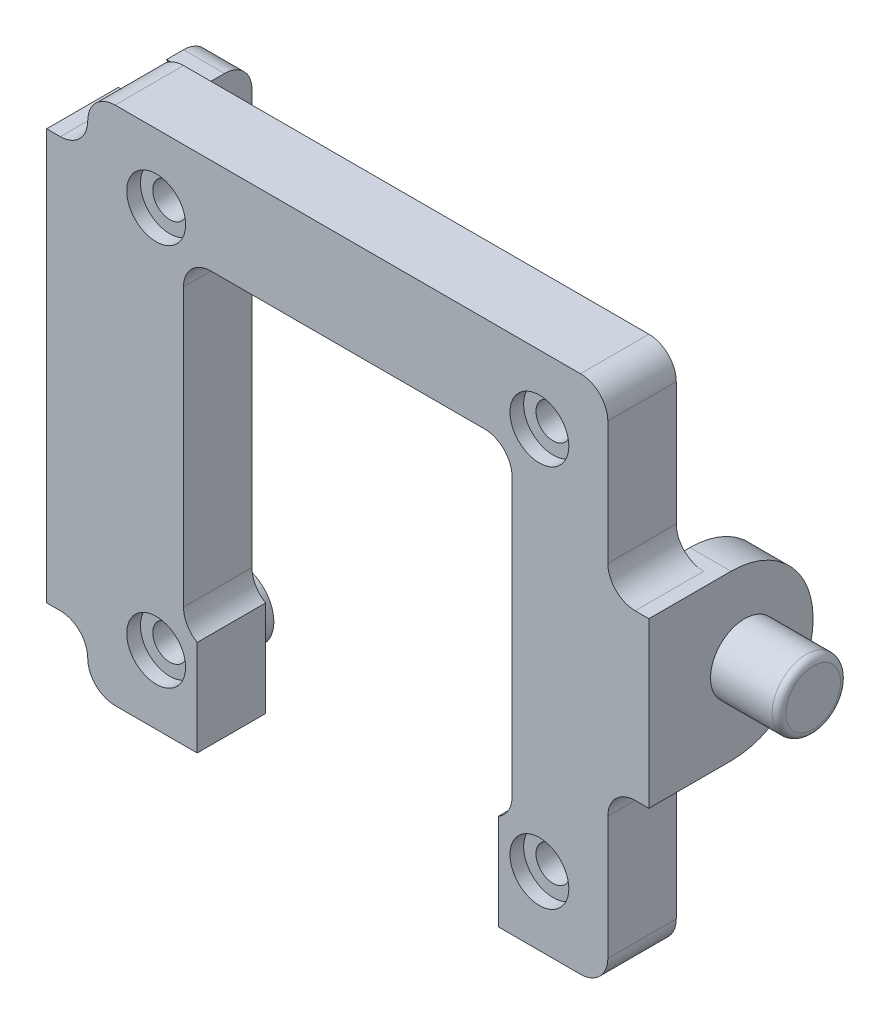
SolidWorks part; units mm, degrees
ref_plane "前视基准面" through (0, 0, 0) normal (0, 0, 1) x (1, 0, 0)
ref_plane "上视基准面" through (0, 0, 0) normal (0, 1, 0) x (1, 0, 0)
ref_plane "右视基准面" through (0, 0, 0) normal (1, 0, 0) x (0, 0, -1)
sketch "草图1" plane through (0, 0, 0) normal (0, 0, 1) x (1, 0, 0)
  line L0 (-14, 14) -> (14, 14) construction
  line L1 (19, -19) -> (12, -19)
  line L2 (19, -19) -> (19, 19)
  line L3 (19, 19) -> (-19, 19)
  line L4 (-19, -19) -> (-19, 19)
  line L5 (19, -19) -> (-19, 19) construction
  line L6 (19, 19) -> (-19, -19) construction
  line L7 (14, 14) -> (14, -14) construction
  line L8 (14, -14) -> (-14, -14) construction
  line L9 (-14, -14) -> (-14, 14) construction
  line L12 (12, -12) -> (12, 12)
  line L13 (12, 12) -> (-12, 12)
  line L14 (-12, -12) -> (-12, 12)
  line L15 (12, -12) -> (-12, 12) construction
  line L16 (12, 12) -> (-12, -12) construction
  line L18 (-12, -19) -> (-19, -19)
  line L19 (-12, -12) -> (-11, -12)
  line L20 (-11, -12) -> (-11, -19)
  line L21 (-11, -19) -> (-12, -19)
  line L22 (12, -12) -> (11, -12)
  line L23 (11, -12) -> (11, -19)
  line L24 (11, -19) -> (12, -19)
  circle A0 centre (-14, 14) radius 1 construction
  circle A1 centre (-14, -14) radius 1 construction
  circle A2 centre (14, -14) radius 1 construction
  circle A3 centre (14, 14) radius 1 construction
  point P0 (0, 0)
  point P14 (0, 0)
  dimension "D4" = 2
  dimension "D1" = 38
  dimension "D2" = 38
  dimension "D3" = 28
  dimension "D5" = 24
  dimension "D6" = 24
  dimension "D7" = 1
extrude "凸台-拉伸1" add sketch "草图1" against normal blind 5
sketch "草图6" plane through (0, 0, 0) normal (0, 0, 1) x (1, 0, 0)
  line L0 (-14, 14) -> (14, 14) construction
  line L5 (14, 14) -> (14, -14) construction
  line L6 (14, -14) -> (-14, -14) construction
  line L7 (-14, -14) -> (-14, 14) construction
  line L8 (-14, 14) -> (14, -14) construction
  line L9 (14, 14) -> (-14, -14) construction
  circle A0 centre (-14, 14) radius 2.5
  circle A1 centre (-14, -14) radius 2.5
  circle A2 centre (14, -14) radius 2.5
  circle A3 centre (14, 14) radius 2.5
  dimension "D4" = 5
  dimension "D1" = 28
  dimension "D2" = 28
extrude "凸台-拉伸5" add sketch "草图6" against normal blind 1.1 from surface starting at face at (0, -5.1667, -5)
hole_wizard "孔1" positions "草图2" profile "草图3" legacy end condition through all
sketch "草图2" plane through (0, 0, 0) normal (0, 0, 1) x (1, 0, 0)
  line L1 (14, -14) -> (-14, -14)
  line L2 (14, -14) -> (14, 14)
  line L3 (14, 14) -> (-14, 14)
  line L4 (-14, -14) -> (-14, 14)
  line L5 (14, -14) -> (-14, 14) construction
  line L6 (14, 14) -> (-14, -14) construction
  point P1 (-14, 14)
  point P148 (14, -14)
  point P149 (14, 14)
  point P150 (-14, -14)
  point P180 (0, 0)
  point P183 (0, 0)
  point P185 (0.0083, -0.0481)
  point P189 (0, 0)
  dimension "D1" = 28
  dimension "D2" = 28
sketch "草图3" plane through (-14, 14, 0) normal (1, 0, 0) x (0, -1, 0)
  line L0 (0, 0) -> (0, 6.1)
  line L1 (0, 6.1) -> (1.25, 6.1)
  line L2 (1.25, 6.1) -> (1.25, 1)
  line L3 (1.25, 1) -> (2.15, 1)
  line L4 (2.15, 1) -> (2.15, 0)
  line L5 (2.15, 0) -> (0, 0)
  line L6 (0, 110) -> (0, -10) construction
  dimension "直径" = 2.5
  dimension "深度" = 6.1
  dimension "柱坑直径" = 4.3
  dimension "柱坑深度" = 1
fillet "圆角1" radius 2 8 edges at (19, -19, -2.5) (19, 19, -2.5) (-19, 19, -2.5) (12, 12, -2.5) (-19, -19, -2.5) (12, -12, -2.5) (-12, -12, -2.5) (-12, 12, -2.5)
sketch "草图5" plane through (-19, 0, 0) normal (-1, 0, 0) x (0, 0, 1)
  line L0 (0, 17) -> (0, -17) construction
  line L1 (-12, -15) -> (0, -15)
  line L2 (-12, -15) -> (-12, 15)
  line L3 (-12, 15) -> (0, 15)
  line L4 (0, -15) -> (0, 15)
  line L5 (-12, -15) -> (0, 15) construction
  line L6 (-12, 15) -> (0, -15) construction
  line L7 (0, 0) -> (-6, 0) construction
  point P0 (-6, 0)
  dimension "D1" = 30
  dimension "D2" = 12
extrude "凸台-拉伸3" add sketch "草图5" along normal blind 3
sketch "草图9" plane through (-22, 0, -24) normal (1, 0, 0) x (0, 0, -1)
  line L0 (-17, 0) -> (-17, -14.05) construction
  line L1 (-18.997, -14.1591) -> (-19.65, -2.2091)
  line L2 (-14.35, -2.2091) -> (-15.003, -14.1591)
  line L3 (-12, 0) -> (-17, 0) construction
  line L4 (-12, 15) -> (-12, -15) construction
  line L5 (-24, -15) -> (-24, 15) construction
  arc A0 (-14.35, -2.2091) -> (-19.65, -2.2091) centre (-17, 0) ccw
  arc A1 (-18.997, -14.1591) -> (-15.003, -14.1591) centre (-17, -14.05) ccw
  dimension "D1" = 6.9
  dimension "D2" = 4
  dimension "D3" = 19.5
  dimension "D4" = 5.3
  dimension "D5" = 7
extrude "切除-拉伸1" cut sketch "草图9" along normal blind 1.4
mirror "镜向2" about plane through (0, 0, 0) normal (0, 1, 0) of "切除-拉伸1"
sketch "草图10" plane through (19, 0, 0) normal (1, 0, 0) x (0, 0, -1)
  line L0 (0, -17) -> (0, 17) construction
  line L1 (0, 6) -> (12, 6)
  line L2 (0, 6) -> (0, -6)
  line L3 (0, -6) -> (12, -6)
  line L4 (12, 6) -> (12, -6)
  line L5 (12, 15) -> (12, -15) construction
  line L6 (0, 0) -> (12, 0) construction
  dimension "D1" = 12
extrude "凸台-拉伸6" add sketch "草图10" along normal blind 3
sketch "草图11" plane through (22, 0, 0) normal (1, 0, 0) x (0, 0, -1)
  line L0 (0, 0) -> (7, 0) construction
  line L4 (0, 6) -> (0, -6)
  line L5 (0, -6) -> (12, -6)
  line L6 (12, -6) -> (12, 6)
  line L7 (12, 6) -> (0, 6)
  line L8 (0, 6) -> (0, -6) construction
  circle A0 centre (7, 0) radius 2.5
  dimension "D3" = 5
  dimension "D2" = 7
  dimension "D1" = 0
extrude "凸台-拉伸7" add sketch "草图11" along normal blind 5
fillet "圆角2" 2 edges at (20.5, 6, -12) (20.5, -6, -12) type full round first side face at (20.2, 6, -5.8) second side face at (20.2, -6, -5.8) middle face at (20.5, 0, -12)
fillet "圆角4" radius 2 4 edges at (19, -6, -2.5) (19, 6, -2.5) (-19, 15, -2.5) (-19, -15, -2.5)
fillet "圆角5" radius 2 2 edges at (-20.5, 15, -12) (-20.5, -15, -12)
fillet "圆角6" radius 0.5 1 edges at (27, 0, -9.5)
